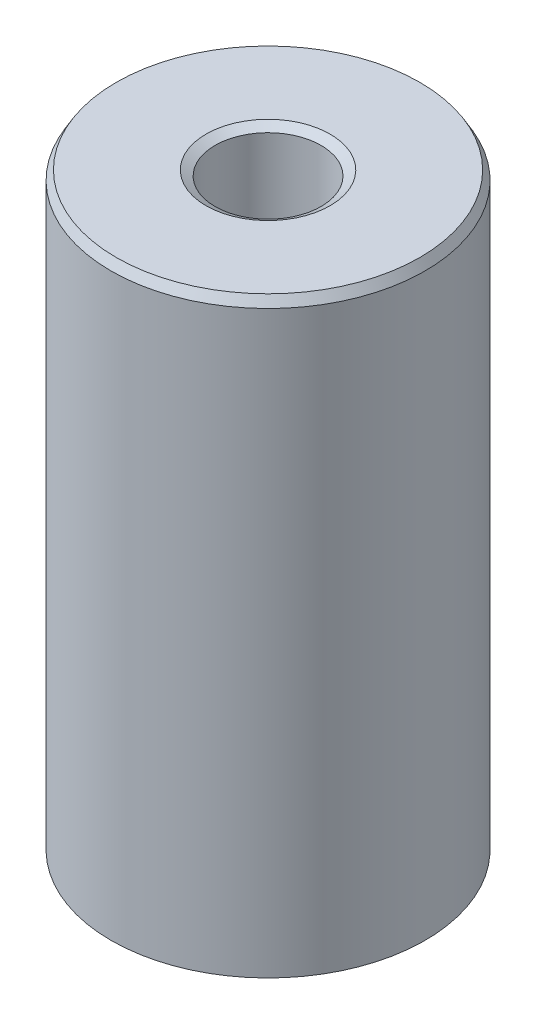
SolidWorks part; units mm, degrees
ref_plane "Front Plane" through (0, 0, 0) normal (0, 0, 1) x (1, 0, 0)
ref_plane "Top Plane" through (0, 0, 0) normal (0, 1, 0) x (1, 0, 0)
ref_plane "Right Plane" through (0, 0, 0) normal (1, 0, 0) x (0, 0, -1)
sketch "Sketch1" plane through (0, 0, 0) normal (0, 1, 0) x (1, 0, 0)
  circle A0 centre (0, 0) radius 10
  dimension "SLEEVE_OD" = 20
extrude "Boss-Extrude1" add sketch "Sketch1" along normal blind 37.8421
sketch "Sketch2" plane through (0, 0, 0) normal (0, 1, 0) x (1, 0, 0)
  circle A0 centre (0, 0) radius 3.3766
  dimension "BORE_D" = 6.7531
extrude "Cut-Extrude1" cut sketch "Sketch2" along normal through all
chamfer "Chamfer1" distance 0.5759 angle 30 4 edges at (0, 37.8421, 3.3766) (0, 0, 3.3766) (0, 0, 10) (0, 37.8421, 10) first distance on face at (0, 37.8421, 3.3766) first distance on face at (0, 0, 3.3766) first distance on face at (0, 37.8421, 10)
